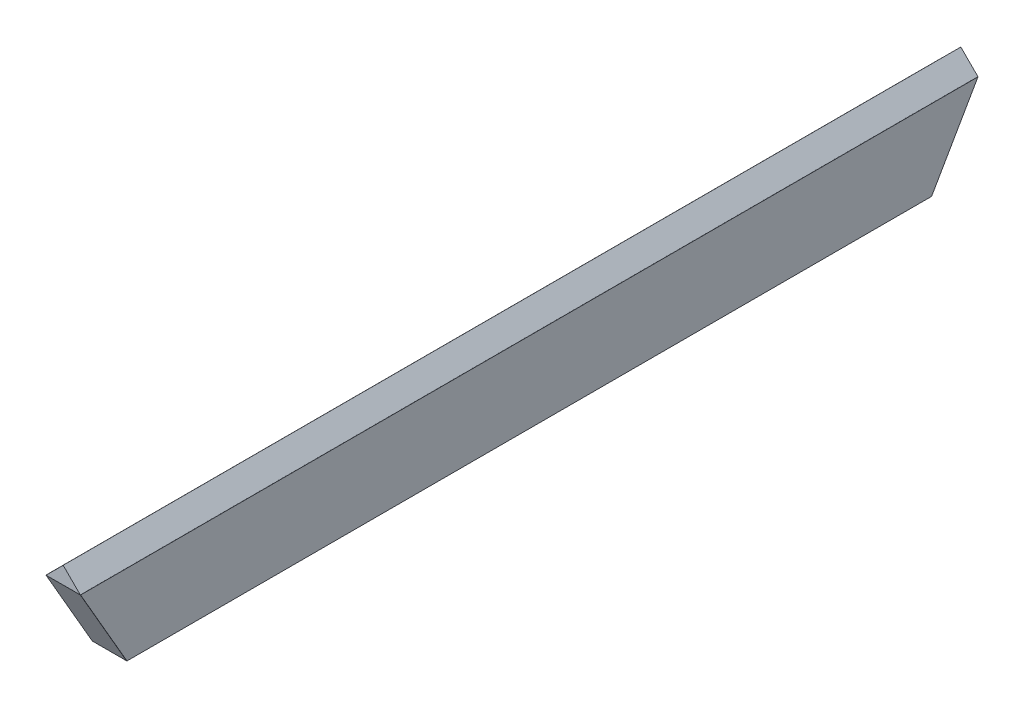
SolidWorks part; units mm, degrees
ref_plane "Front Plane" through (0, 0, 0) normal (0, 0, 1) x (1, 0, 0)
ref_plane "Top Plane" through (0, 0, 0) normal (0, 1, 0) x (1, 0, 0)
ref_plane "Right Plane" through (0, 0, 0) normal (1, 0, 0) x (0, 0, -1)
sketch "Sketch1" plane through (0, 0, 0) normal (0, 0, 1) x (1, 0, 0)
  line L1 (1.5, -3.5) -> (-1.5, -3.5)
  line L2 (1.5, -3.5) -> (1.5, 3.5)
  line L3 (1.5, 3.5) -> (-1.5, 3.5)
  line L4 (-1.5, -3.5) -> (-1.5, 3.5)
  line L5 (1.5, -3.5) -> (-1.5, 3.5) construction
  line L6 (1.5, 3.5) -> (-1.5, -3.5) construction
  point P0 (0, 0)
  dimension "D1" = 7
  dimension "D2" = 3
extrude "Boss-Extrude1" add sketch "Sketch1" along normal mid plane 78
draft "Draft1" type of draft neutral plane draft angle 30 faces to draft 1 face at (0, 0, 39) neutral plane through (1.5, 3.5, 39) neutral plane normal (0, 1, 0) reverse direction yes parameters "D1"=30
draft "Draft2" type of draft neutral plane draft angle 30 faces to draft 1 face at (0, 0, -39) neutral plane through (1.5, 3.5, 39) neutral plane normal (0, 1, 0) reverse direction yes parameters "D1"=30
chamfer "Chamfer1" distance 0.01 angle 45 4 edges at (-1.5, 3.5, 0) (1.5, 3.5, 0) (-1.5, -3.5, 0) (1.5, -3.5, 0)
chamfer "Chamfer2" distance 0.01 angle 45 14 edges at (1.495, 3.495, 38.9971) (1.5, 0, 36.9793) (0, -3.5, 34.9585) (-1.5, 0, 36.9793) (-1.495, 3.495, 38.9971) (0, 3.5, 39) (-1.495, -3.495, -34.9614) (0, -3.5, -34.9585) (1.495, -3.495, -34.9614) (1.5, 0, -36.9793) (1.495, 3.495, -38.9971) (0, 3.5, -39) (-1.495, 3.495, -38.9971) (-1.5, 0, -36.9793)
sketch "Sketch2" plane through (0, 0, 0) normal (0, 0, 1) x (1, 0, 0)
  line L0 (1.4867, 3.5) -> (0, 4.9832)
  line L1 (0, 4.9832) -> (-1.49, 3.4897)
  line L2 (-1.49, 3.4897) -> (1.4867, 3.5)
  point P3 (0, 4.1166)
extrude "Boss-Extrude2" add sketch "Sketch2" against normal up to vertex (38.9892 mm away) from vertex at 38.9963 starting at point (1.4861, 3.4937, 38.9963)
